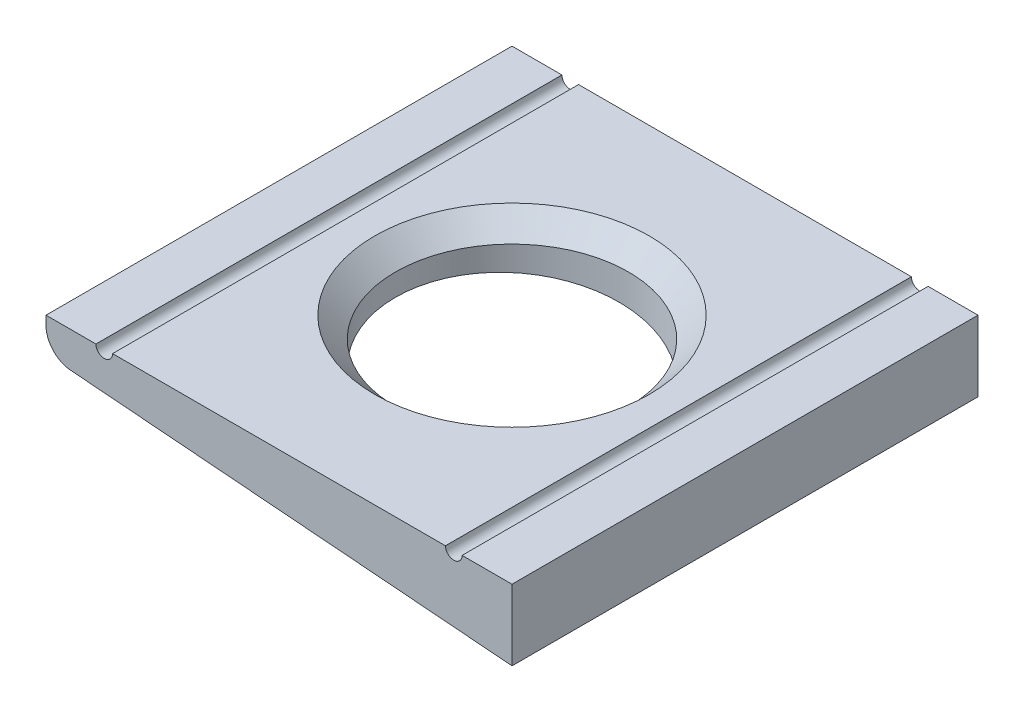
SolidWorks part; units mm, degrees
extrude "Base-Extrude" add sketch "Sketch1" along normal mid plane 56
sketch "Sketch1" plane through (0, 0, 0) normal (0, 0, 1) x (1, 0, 0)
  line L0 (28, 0) -> (-28, 0)
  line L1 (28, 0) -> (28, -8.5)
  line L2 (-28, 0) -> (-28, -1.0658)
  line L3 (28, -8.5) -> (-25.0552, -4.2556)
  line L4 (0, 0) -> (0, -6.26) construction
  arc A0 (-25.0552, -4.2556) -> (-28, -1.0658) centre (-24.8, -1.0658) cw
  dimension "D2" = 28
ref_plane "Plane1" through (0, 0, 0) normal (0, 0, 1) x (1, 0, 0)
ref_plane "Plane2" through (0, 0, 0) normal (0, 1, 0) x (1, 0, 0)
ref_plane "Plane3" through (0, 0, 0) normal (1, 0, 0) x (0, 0, -1)
sketch "Sketch2" plane through (0, 0, 0) normal (0, 1, 0) x (-1, 0, 0)
  circle A0 centre (0, 0) radius 14
extrude "Cut-Extrude1" cut sketch "Sketch2" against normal through all
sketch "Sketch3" plane through (0, 0, 28) normal (0, 0, 1) x (1, 0, 0)
  line L0 (28, 0) -> (-28, 0) construction
  circle A0 centre (21, 0) radius 1
  circle A1 centre (-21, 0) radius 1
  dimension "T" = 1
  dimension "D1" = 1
  dimension "D2" = 21
  dimension "D3" = 21
extrude "ID-Grooves" cut sketch "Sketch3" against normal through all
chamfer "Chamfer1" distance 2.5 angle 45 1 edges at (-14, 0, 0)
equation "\"D2@Sketch1\" = \"B@Sketch1\" / 2"
equation "\"D2@Sketch3\" =  ( \"D@Sketch2\" / 2 )  +  ( \"B@Sketch1\" -  \"D@Sketch2\" )  / 4"
equation "\"D3@Sketch3\" = \"D2@Sketch3\""
equation "\"D1@Sketch3\" = \"T@Sketch3\""
